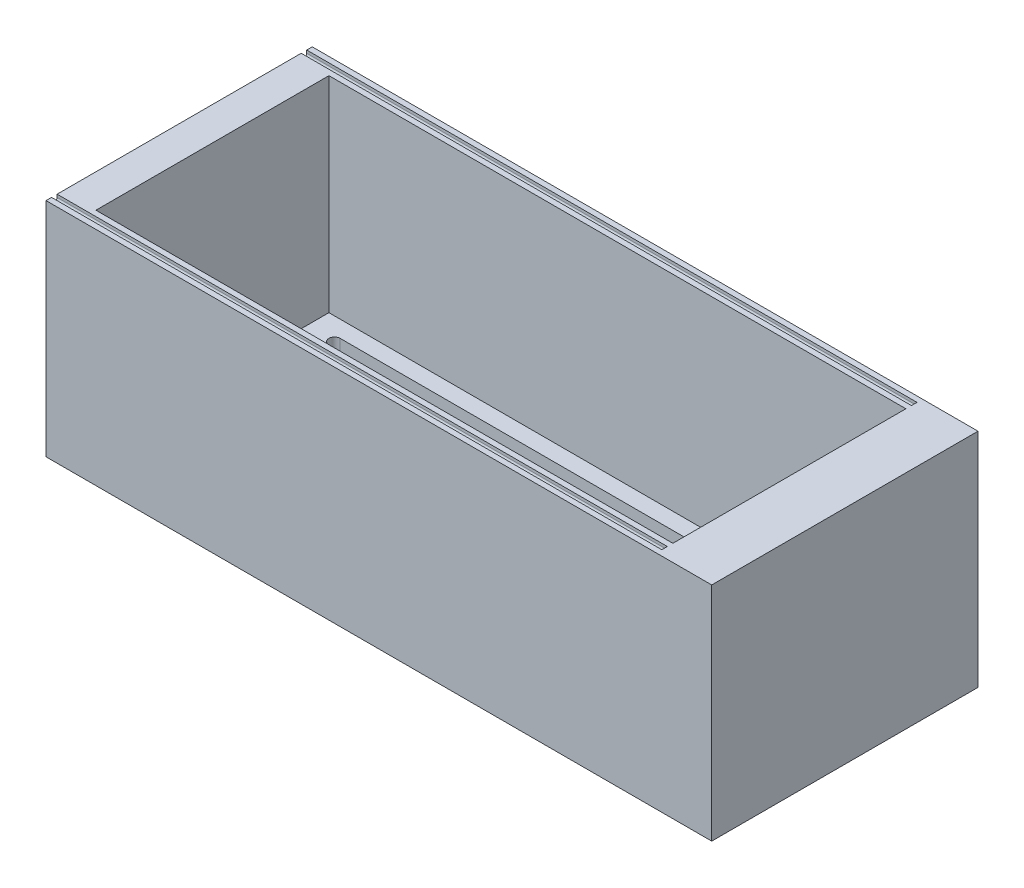
SolidWorks part; units mm, degrees
ref_plane "Front Plane" through (0, 0, 0) normal (0, 0, 1) x (1, 0, 0)
ref_plane "Top Plane" through (0, 0, 0) normal (0, 1, 0) x (1, 0, 0)
ref_plane "Right Plane" through (0, 0, 0) normal (1, 0, 0) x (0, 0, -1)
sketch "Sketch1" plane through (0, 0, 0) normal (0, 1, 0) x (1, 0, 0)
  line L1 (0, 0) -> (120, 0)
  line L2 (0, 0) -> (0, 48)
  line L3 (0, 48) -> (120, 48)
  line L4 (120, 0) -> (120, 48)
  dimension "D1" = 120
  dimension "D2" = 48
extrude "Boss-Extrude1" add sketch "Sketch1" along normal blind 40
sketch "Sketch2" plane through (0, 40, 0) normal (0, 1, 0) x (1, 0, 0)
  line L1 (6, 48) -> (74, 48)
  line L2 (6, 48) -> (6, 45)
  line L3 (6, 45) -> (74, 45)
  line L4 (74, 48) -> (74, 45)
  line L5 (120, 0) -> (120, 48) construction
  line L6 (0, 48) -> (120, 48) construction
  dimension "D1" = 3
  dimension "D2" = 46
  dimension "D3" = 68
extrude "Boss-Extrude2" [suppressed] add sketch "Sketch2" along normal blind 15
sketch "Sketch3" plane through (0, 40, 0) normal (0, 1, 0) x (1, 0, 0)
  line L1 (110, 45) -> (6, 45)
  line L2 (110, 45) -> (110, 3)
  line L3 (110, 3) -> (6, 3)
  line L4 (6, 45) -> (6, 3)
  line L5 (120, 0) -> (120, 48) construction
  line L6 (0, 0) -> (120, 0) construction
  line L7 (0, 48) -> (120, 48) construction
  dimension "D1" = 104
  dimension "D2" = 10
  dimension "D3" = 3
  dimension "D4" = 3
extrude "Cut-Extrude1" cut sketch "Sketch3" against normal blind 37
sketch "Sketch5" plane through (0, 3, 0) normal (0, 1, 0) x (1, 0, 0)
  line L0 (11, 41) -> (105, 41) construction
  line L1 (11, 42) -> (105, 42)
  line L2 (11, 40) -> (105, 40)
  line L3 (6, 45) -> (6, 3) construction
  line L4 (110, 3) -> (110, 45) construction
  line L5 (110, 45) -> (6, 45) construction
  line L8 (11, 35.1) -> (105, 35.1)
  line L11 (11, 37.1) -> (105, 37.1)
  line L14 (11, 36.1) -> (105, 36.1) construction
  line L17 (11, 30.2) -> (105, 30.2)
  line L20 (11, 32.2) -> (105, 32.2)
  line L23 (11, 31.2) -> (105, 31.2) construction
  line L26 (11, 25.3) -> (105, 25.3)
  line L28 (11, 27.3) -> (105, 27.3)
  line L29 (11, 26.3) -> (105, 26.3) construction
  line L30 (11, 20.4) -> (105, 20.4)
  line L31 (11, 22.4) -> (105, 22.4)
  line L32 (11, 21.4) -> (105, 21.4) construction
  line L33 (11, 15.5) -> (105, 15.5)
  line L34 (11, 17.5) -> (105, 17.5)
  line L35 (11, 16.5) -> (105, 16.5) construction
  line L36 (11, 10.6) -> (105, 10.6)
  line L37 (11, 12.6) -> (105, 12.6)
  line L38 (11, 11.6) -> (105, 11.6) construction
  line L39 (11, 5.7) -> (105, 5.7)
  line L40 (11, 7.7) -> (105, 7.7)
  line L41 (11, 6.7) -> (105, 6.7) construction
  arc A0 (11, 42) -> (11, 40) centre (11, 41) ccw
  arc A1 (105, 40) -> (105, 42) centre (105, 41) ccw
  arc A16 (11, 37.1) -> (11, 35.1) centre (11, 36.1) ccw
  arc A17 (105, 35.1) -> (105, 37.1) centre (105, 36.1) ccw
  arc A18 (11, 32.2) -> (11, 30.2) centre (11, 31.2) ccw
  arc A19 (105, 30.2) -> (105, 32.2) centre (105, 31.2) ccw
  arc A20 (11, 27.3) -> (11, 25.3) centre (11, 26.3) ccw
  arc A21 (105, 25.3) -> (105, 27.3) centre (105, 26.3) ccw
  arc A22 (11, 22.4) -> (11, 20.4) centre (11, 21.4) ccw
  arc A23 (105, 20.4) -> (105, 22.4) centre (105, 21.4) ccw
  arc A24 (11, 17.5) -> (11, 15.5) centre (11, 16.5) ccw
  arc A25 (105, 15.5) -> (105, 17.5) centre (105, 16.5) ccw
  arc A26 (11, 12.6) -> (11, 10.6) centre (11, 11.6) ccw
  arc A27 (105, 10.6) -> (105, 12.6) centre (105, 11.6) ccw
  arc A28 (11, 7.7) -> (11, 5.7) centre (11, 6.7) ccw
  arc A29 (105, 5.7) -> (105, 7.7) centre (105, 6.7) ccw
  point P2 (58, 41)
  point P17 (58, 36.1)
  point P24 (58, 31.2)
  point P31 (58, 26.3)
  point P38 (58, 21.4)
  point P45 (58, 16.5)
  point P52 (58, 11.6)
  point P59 (58, 6.7)
  dimension "D1" = 1
  dimension "D2" = 5
  dimension "D3" = 5
  dimension "D4" = 3
  dimension "D5" = 8
extrude "Cut-Extrude2" cut sketch "Sketch5" against normal blind 37
sketch "Sketch7" plane through (0, 0, 0) normal (-1, 0, 0) x (0, 0, 1)
  line L0 (-1.5, 39.5) -> (-1.5, 40.5) construction
  line L2 (-2, 39.5) -> (-2, 40.5)
  line L3 (-1, 39.5) -> (-1, 40.5)
  line L6 (-48, 40) -> (0, 40) construction
  line L7 (0, 40) -> (0, 0) construction
  arc A0 (-2, 39.5) -> (-1, 39.5) centre (-1.5, 39.5) ccw
  arc A1 (-1, 40.5) -> (-2, 40.5) centre (-1.5, 40.5) ccw
  point P4 (-1.5, 40)
  dimension "D2" = 0.5
  dimension "D1" = 1.5
  dimension "D3" = 1
extrude "Cut-Extrude4" cut sketch "Sketch7" against normal blind 110
ref_plane "Plane1" through (0, 0, -24) normal (0, 0, -1) x (-1, 0, 0)
mirror "Mirror1" about plane through (0, 0, -24) normal (0, 0, -1) of "Cut-Extrude4"
sketch "Sketch8" plane through (0, 0, 0) normal (-1, 0, 0) x (0, 0, 1)
  line L0 (-48.5, 1.5) -> (-47.5, 1.5) construction
  line L1 (-48.5, 2) -> (-47.5, 2)
  line L2 (-48.5, 1) -> (-47.5, 1)
  line L3 (-48, 40) -> (-48, 0) construction
  line L4 (-48, 0) -> (0, 0) construction
  arc A0 (-48.5, 2) -> (-48.5, 1) centre (-48.5, 1.5) ccw
  arc A1 (-47.5, 1) -> (-47.5, 2) centre (-47.5, 1.5) ccw
  point P2 (-48, 1.5)
  dimension "D2" = 0.5
  dimension "D1" = 1
  dimension "D3" = 1.5
extrude "Cut-Extrude5" cut sketch "Sketch8" against normal blind 110
sketch "Sketch6" [suppressed] plane through (74, 0, 0) normal (1, 0, 0) x (0, 0, -1)
  line L1 (48, 40) -> (47, 40)
  line L2 (48, 40) -> (48, 45.2)
  line L3 (48, 45.2) -> (47, 45.2)
  line L4 (47, 40) -> (47, 45.2)
  dimension "D1" = 5.2
  dimension "D2" = 1
